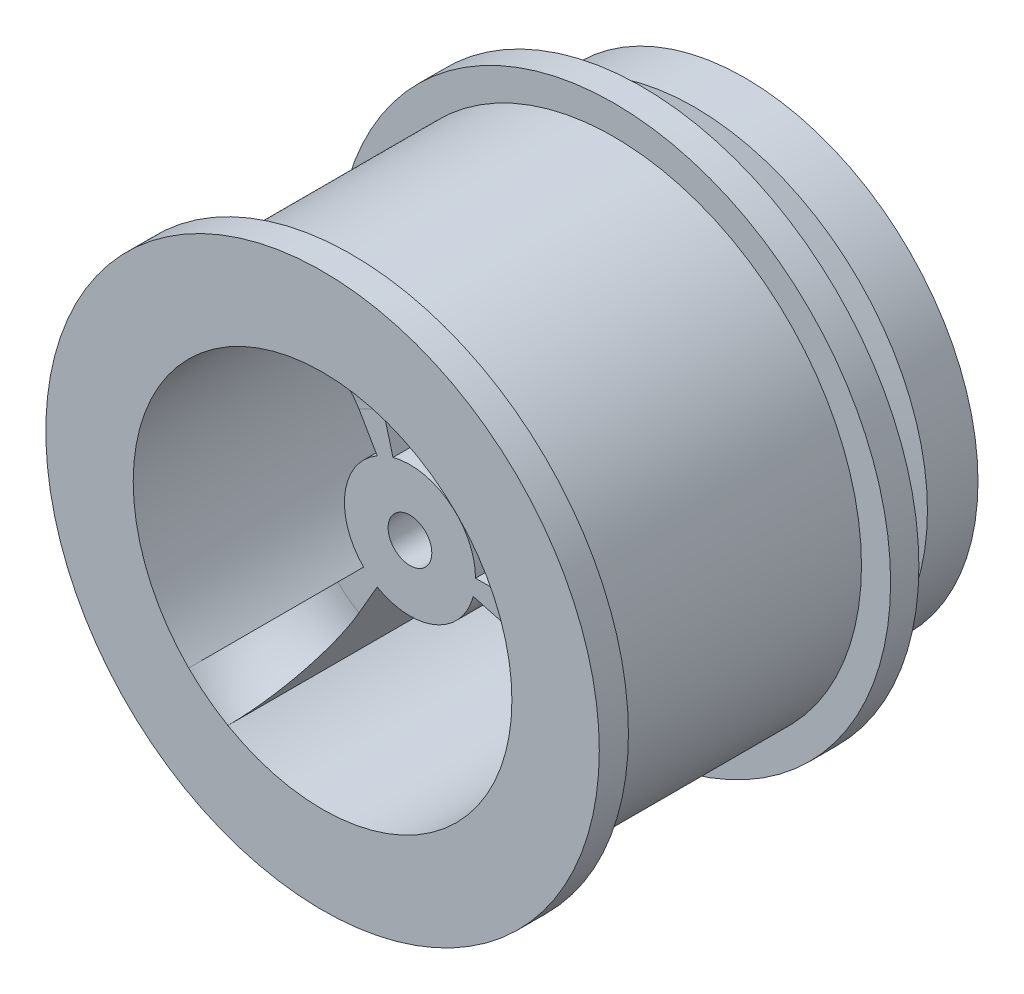
SolidWorks part; units mm, degrees
ref_plane "Front Plane" through (0, 0, 0) normal (0, 0, 1) x (1, 0, 0)
ref_plane "Top Plane" through (0, 0, 0) normal (0, 1, 0) x (1, 0, 0)
ref_plane "Right Plane" through (0, 0, 0) normal (1, 0, 0) x (0, 0, -1)
sketch "Sketch1" plane through (0, 0, 0) normal (0, 0, 1) x (1, 0, 0)
  line L0 (0, 0) -> (0, 8.5) construction
  circle A0 centre (0, 0) radius 6.5
  circle A1 centre (0, 0) radius 8.5
  circle A2 centre (0, 0) radius 0.75
  circle A3 centre (0, 0) radius 2.25
  dimension "D1" = 17
  dimension "D2" = 2
  dimension "D3" = 1.5
  dimension "D4" = 1.5
extrude "Boss-Extrude1" add sketch "Sketch1" along normal blind 9 contours A2 A3 | A0 A1 region at (-8.2596, 0, 0) region at (-2.1864, 0, 0)
sketch "Sketch2" plane through (0, 0, 0) normal (0, 0, -1) x (-1, 0, 0)
  circle A0 centre (0, 0) radius 9.5
  dimension "D1" = 19
extrude "Boss-Extrude2" add sketch "Sketch2" along normal blind 1.5
sketch "Sketch3" plane through (0, 0, 9) normal (0, 0, 1) x (1, 0, 0)
  circle A0 centre (0, 0) radius 6.5
  circle A1 centre (0, 0) radius 9.5
  circle A2 centre (0, 0) radius 6.5 construction
  dimension "D1" = 19
extrude "Boss-Extrude3" add sketch "Sketch3" along normal blind 1
sketch "Sketch5" plane through (0, 0, 9) normal (0, 0, 1) x (1, 0, 0)
  line L0 (0, 0) -> (13.9199, 0) construction
  line L1 (0, 0) -> (12.6765, -3.3967) construction
  line L2 (2.25, 0) -> (6.5, 0)
  line L3 (2.1733, -0.5823) -> (6.2785, -1.6823)
  arc A0 (2.1733, -0.5823) -> (2.25, 0) centre (0, 0) ccw
  circle A1 centre (0, 0) radius 2.25 construction
  arc A2 (6.2785, -1.6823) -> (6.5, 0) centre (0, 0) ccw
  circle A3 centre (0, 0) radius 6.5 construction
  dimension "D1" = 15
extrude "Boss-Extrude4" add sketch "Sketch5" against normal up to next
pattern_circular "CirPattern1" count 3 over 360 about axis through (0, 0, 9) along (0, 0, 1) of "Boss-Extrude4"
sketch "Sketch6" plane through (0, 0, 9) normal (0, 0, 1) x (1, 0, 0)
  circle A0 centre (0, 0) radius 6.5
  arc A2 (-4.5962, -4.5962) -> (-3.25, -5.6292) centre (0, 0) ccw construction
extrude "Cut-Extrude2" cut sketch "Sketch6" against normal blind 2
fillet "Fillet1" radius 3 3 edges at (-2.4874, 6.0052, 7) (-3.9569, -5.1568, 7) (6.4444, -0.8484, 7)
sketch "Sketch8" plane through (0, 0, -1.5) normal (0, 0, -1) x (-1, 0, 0)
  circle A1 centre (0, 0) radius 6.5
  dimension "D1" = 13
extrude "Boss-Extrude5" add sketch "Sketch8" along normal blind 1 contours A1
sketch "Sketch11" plane through (0, 0, -2.5) normal (0, 0, -1) x (-1, 0, 0)
  circle A0 centre (0, 0) radius 8
  dimension "D1" = 16
extrude "Boss-Extrude6" add sketch "Sketch11" along normal blind 2
sketch "Sketch7" plane through (0, 0, 0) normal (0, 0, 1) x (1, 0, 0)
  line L0 (0, 0) -> (12.1676, 0) construction
  line L1 (0, 0) -> (6.4881, -15.6637) construction
  circle A0 centre (1.7221, -4.1575) radius 1
  dimension "D2" = 2
  dimension "D3" = 4.5
  dimension "D1" = 67.5
extrude "Cut-Extrude3" cut sketch "Sketch7" against normal blind 7
fillet "Fillet2" radius 1 12 edges at (0.861, -2.0787, 0) (1.3697, 1.785, 0) (-2.2308, 0.2937, 0) (3.9569, 5.1568, 0) (2.4874, -6.0052, 0) (-6.4444, 0.8484, 0) (4.375, 0, 0) (4.2259, -1.1323, 0) (-3.0936, -3.0936, 0) (-2.1875, -3.7889, 0) (-1.1323, 4.2259, 0) (-2.1875, 3.7889, 0)
pattern_circular "CirPattern2" count 3 over 360 about axis through (0, 0, 7) along (0, 0, 1) of "Cut-Extrude3"
sketch "Sketch4" plane through (0, 0, 7) normal (0, 0, 1) x (1, 0, 0)
  circle A0 centre (0, 0) radius 0.75
  arc A1 (2.25, 0) -> (-0.5823, 2.1733) centre (0, 0) ccw construction
  dimension "D1" = 1.5
extrude "Cut-Extrude4" cut sketch "Sketch4" against normal blind 20
sketch "Sketch12" plane through (0, 0, 0) normal (0, 1, 0) x (1, 0, 0)
  line L0 (6.5, 2.5) -> (10.5, 3.2053)
  line L1 (10.5, 3.2053) -> (10.5, 0.7947)
  line L2 (10.5, 0.7947) -> (6.5, 1.5)
  line L3 (6.5, 1.5) -> (6.5, 2.5)
  line L4 (0, 0) -> (0, 8.195) construction
  dimension "D1" = 4
  dimension "D2" = 100
  dimension "D3" = 100
revolve "Cut-Revolve1" cut sketch "Sketch12" angle 360 about L4
